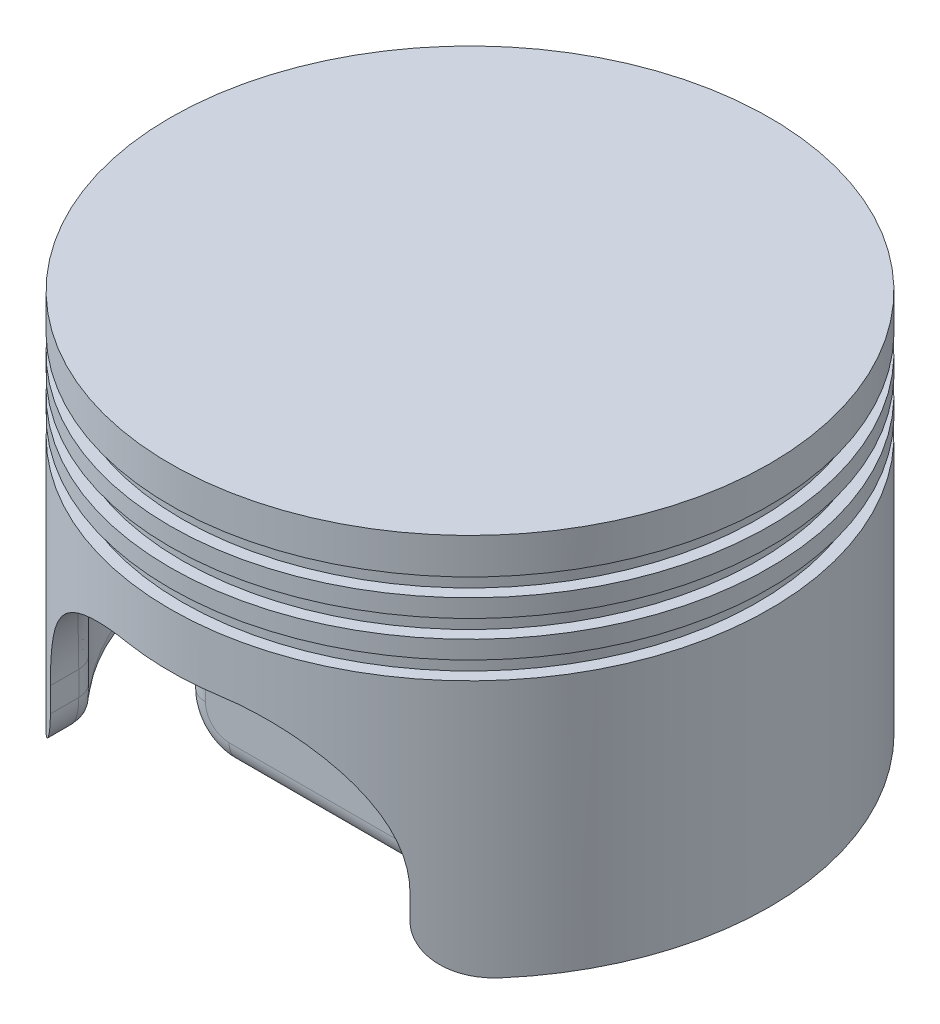
SolidWorks part; units mm, degrees
ref_plane "Front Plane" through (0, 0, 0) normal (0, 0, 1) x (1, 0, 0)
ref_plane "Top Plane" through (0, 0, 0) normal (0, 1, 0) x (1, 0, 0)
ref_plane "Right Plane" through (0, 0, 0) normal (1, 0, 0) x (0, 0, -1)
sketch "Sketch1" plane through (0, 0, 0) normal (0, 0, 1) x (1, 0, 0)
  line L0 (0, 0) -> (0, -19)
  line L1 (0, -19) -> (57.15, -19)
  line L2 (57.15, -19) -> (57.15, -81.28)
  line L3 (57.15, -81.28) -> (63.5, -81.28)
  line L4 (63.5, -81.28) -> (63.5, 0)
  line L5 (63.5, 0) -> (0, 0)
  dimension "D1" = 63.5
  dimension "D2" = 81.28
  dimension "D3" = 19
  dimension "D4" = 57.15
revolve "Revolve1" add sketch "Sketch1" angle 360 about L0
sketch "Sketch2" plane through (0, 0, 0) normal (0, 0, 1) x (1, 0, 0)
  line L5 (-63.5, -81.28) -> (63.5, -81.28) construction
  line L6 (-38.1, -81.28) -> (38.1, -81.28)
  line L7 (-38.1, -81.28) -> (-38.1, -38.1)
  line L8 (-38.1, -38.1) -> (38.1, -38.1)
  line L9 (38.1, -81.28) -> (38.1, -38.1)
  line L10 (-38.1, -81.28) -> (38.1, -38.1) construction
  line L11 (-38.1, -38.1) -> (38.1, -81.28) construction
  point P0 (0, -59.69)
  point P7 (0, 0)
  dimension "D1" = 76.2
  dimension "D2" = 43.18
extrude "Cut-Extrude1" cut sketch "Sketch2" against normal through all both and the other way through all
sketch "Sketch3" plane through (0, 0, 0) normal (0, 0, 1) x (1, 0, 0)
  line L0 (0, 0) -> (0, -29.7598) construction
  line L2 (60.96, -7.62) -> (74.0984, -7.62)
  line L3 (60.96, -7.62) -> (60.96, -11.43)
  line L4 (60.96, -11.43) -> (74.0984, -11.43)
  line L5 (74.0984, -7.62) -> (74.0984, -11.43)
  line L6 (60.96, -7.62) -> (74.0984, -11.43) construction
  line L7 (60.96, -11.43) -> (74.0984, -7.62) construction
  line L8 (63.5, -81.28) -> (63.5, 0) construction
  line L9 (63.5, 0) -> (-63.5, 0) construction
  point P3 (67.5292, -9.525)
  dimension "D1" = 3.81
  dimension "D2" = 2.54
  dimension "D3" = 7.62
revolve "Cut-Revolve1" cut sketch "Sketch3" angle 360 about L0
pattern_linear "LPattern1" count 3 spacing 7.62 along (0, -1, 0) of "Cut-Revolve1"
sketch "Sketch5" plane through (0, -19, 0) normal (0, -1, 0) x (1, 0, 0)
  line L0 (0, 0) -> (-35.422, 0) construction
  line L1 (-30.1, -11.939) -> (30.1, -11.939)
  line L2 (-30.1, 30.939) -> (30.1, 30.939)
  line L3 (-30.1, 30.939) -> (-30.1, 11.939)
  line L4 (-30.1, 11.939) -> (30.1, 11.939)
  line L5 (30.1, 30.939) -> (30.1, 11.939)
  line L6 (-30.1, 30.939) -> (30.1, 11.939) construction
  line L7 (-30.1, 11.939) -> (30.1, 30.939) construction
  line L8 (30.1, -30.939) -> (30.1, -11.939)
  line L9 (-30.1, -30.939) -> (30.1, -30.939)
  line L10 (-30.1, -30.939) -> (-30.1, -11.939)
  point P3 (0, 21.439)
  point P8 (0, 0)
  dimension "D1" = 19
  dimension "D2" = 60.2
extrude "Boss-Extrude4" add sketch "Sketch5" along normal blind 63.5
sketch "Sketch7" plane through (0, 0, 30.939) normal (0, 0, 1) x (1, 0, 0)
  line L0 (30.1, -82.5) -> (-30.1, -82.5) construction
  circle A0 centre (0, -57.1) radius 12.7
  dimension "D1" = 25.4
  dimension "D2" = 25.4
extrude "Cut-Extrude2" cut sketch "Sketch7" against normal through all both
fillet "Fillet1" radius 28 4 edges at (38.1, -38.1, -46.6985) (-38.1, -38.1, -46.6985) (-38.1, -38.1, 46.6985) (38.1, -38.1, 46.6985)
fillet "Fillet2" radius 10 8 edges at (38.1, -81.28, 46.6985) (-38.1, -81.28, 46.6985) (-38.1, -81.28, -46.6985) (38.1, -81.28, -46.6985) (30.1, -82.5, 21.439) (-30.1, -82.5, 21.439) (-30.1, -82.5, -21.439) (30.1, -82.5, -21.439)
fillet "Fillet4" radius 5 36 edges at (40.816, -78.1316, 40.0022) (38.1, -68.69, 42.5971) (33.8387, -51.2516, 46.055) (0, -38.1, 57.15) (-26.8841, -43.6881, 50.4318) (-38.1, -68.69, 42.5971) (-39.4335, -76.2692, 41.3657) (-57.15, -81.28, 0) (-40.816, -78.1316, -40.0022) (-38.1, -68.69, -42.5971) (-33.8387, -51.2516, -46.055) (0, -38.1, -57.15) (26.8841, -43.6881, -50.4318) (38.1, -68.69, -42.5971) (39.4335, -76.2692, -41.3657) (30.1, -45.75, 30.939) (27.1711, -79.5711, 30.939) (-30.1, -45.75, 30.939) (-27.1711, -79.5711, 30.939) (-30.1, -45.75, 11.939) (-27.1711, -79.5711, 11.939) (30.1, -45.75, 11.939) (27.1711, -79.5711, 11.939) (30.1, -45.75, -11.939) (27.1711, -79.5711, -11.939) (-30.1, -45.75, -11.939) (-27.1711, -79.5711, -11.939) (-30.1, -45.75, -30.939) (-27.1711, -79.5711, -30.939) (30.1, -45.75, -30.939) (27.1711, -79.5711, -30.939) (57.15, -81.28, 0) (0, -82.5, 30.939) (0, -82.5, 11.939) (0, -82.5, -11.939) (0, -82.5, -30.939)
fillet "Fillet5" radius 5 17 edges at (-28.6355, -19, -29.4746) (0, -19, -30.939) (28.6355, -19, -29.4746) (30.1, -19, -21.439) (28.6355, -19, -13.4035) (0, -19, -11.939) (-28.6355, -19, -13.4035) (-30.1, -19, -21.439) (-57.15, -19, 0) (28.6355, -19, 29.4746) (0, -19, 30.939) (-28.6355, -19, 29.4746) (-30.1, -19, 21.439) (-28.6355, -19, 13.4035) (0, -19, 11.939) (28.6355, -19, 13.4035) (30.1, -19, 21.439)
